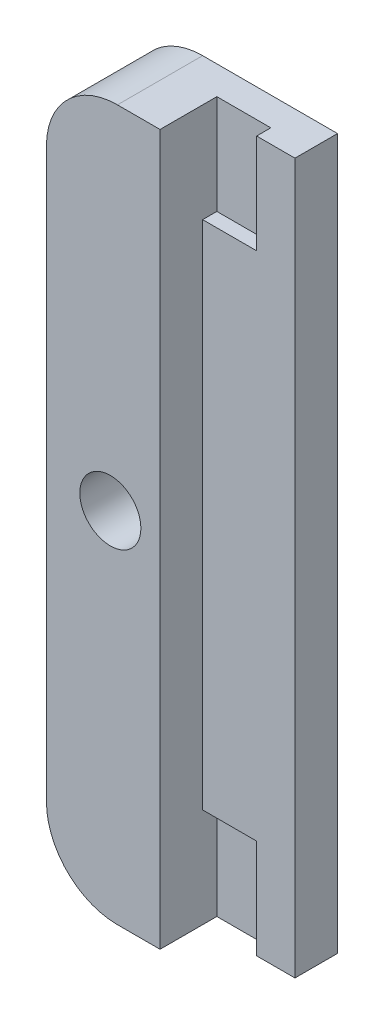
SolidWorks part; units mm, degrees
material "acero"
ref_plane "Alzado" through (0, 0, 0) normal (0, 0, 1) x (1, 0, 0)
ref_plane "Planta" through (0, 0, 0) normal (0, 1, 0) x (1, 0, 0)
ref_plane "Vista lateral" through (0, 0, 0) normal (1, 0, 0) x (0, 0, -1)
sketch "Croquis1" plane through (0, 0, 0) normal (0, 0, 1) x (1, 0, 0)
  line L0 (-4.5, 0) -> (10, 0) construction
  line L1 (-4.5, 25) -> (10, 25)
  line L2 (-4.5, 25) -> (-4.5, -25)
  line L3 (-4.5, -25) -> (10, -25)
  line L4 (10, 25) -> (10, -25)
  circle A0 centre (0, 0) radius 2.15
  dimension "D4" = 4.3
  dimension "D1" = 4.5
  dimension "D2" = 10
  dimension "D3" = 50
extrude "Saliente-Extruir1" add sketch "Croquis1" along normal blind 6
sketch "Croquis3" plane through (0, -25, 0) normal (0, -1, 0) x (1, 0, 0)
  line L1 (10, 3) -> (3.5, 3)
  line L2 (10, 6) -> (10, 0) construction
  line L7 (3.5, 3) -> (3.5, 6)
  line L8 (-4.5, 6) -> (10, 6) construction
  line L9 (3.5, 6) -> (10, 6)
  line L10 (10, 6) -> (10, 3)
  dimension "D1" = 3
  dimension "D2" = 6.5
extrude "Cortar-Extruir1" cut sketch "Croquis3" against normal up to surface (50 mm away) up to face at (2.75, 25, 3)
sketch "Croquis4" plane through (0, 25, 0) normal (0, 1, 0) x (1, 0, 0)
  line L0 (10, -3) -> (3.5, -3) construction
  line L1 (7.3, -3) -> (3.5, -3)
  line L2 (7.3, -3) -> (7.3, -2)
  line L3 (7.3, -2) -> (3.5, -2)
  line L4 (3.5, -3) -> (3.5, -2)
  line L5 (3.5, -3) -> (3.5, -6) construction
  dimension "D1" = 1
  dimension "D2" = 3.8
extrude "Cortar-Extruir2" cut sketch "Croquis4" against normal blind 7
extrude "Cortar-Extruir3" cut sketch "Croquis4<2>" along normal blind 7 from surface starting at face at (3, -25, 3)
sketch "Croquis4<2>" plane through (0, 25, 0) normal (0, 1, 0) x (1, 0, 0) same geometry as "Croquis4"
fillet "Redondeo1" radius 5 2 edges at (-4.5, 25, 3) (-4.5, -25, 3)
